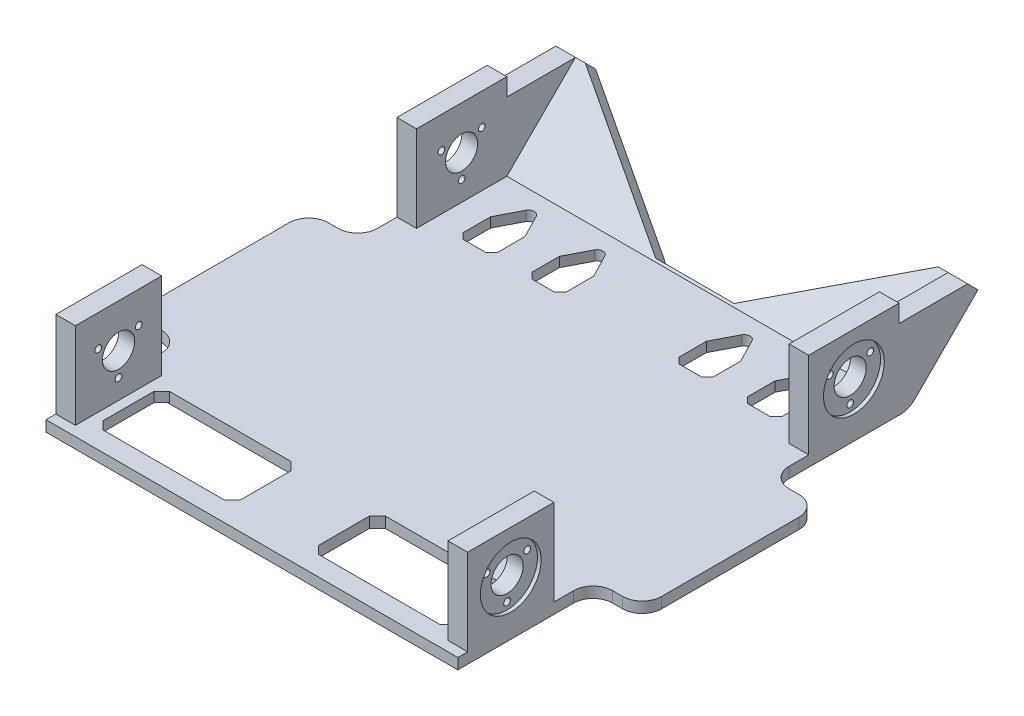
SolidWorks part; units mm, degrees
ref_plane "前视基准面" through (0, 0, 0) normal (0, 0, 1) x (1, 0, 0)
ref_plane "上视基准面" through (0, 0, 0) normal (0, 1, 0) x (1, 0, 0)
ref_plane "右视基准面" through (0, 0, 0) normal (1, 0, 0) x (0, 0, -1)
sketch "草图1" plane through (0, 0, 0) normal (0, 1, 0) x (1, 0, 0)
  line L0 (0, 0) -> (210, 0)
  line L1 (210, 0) -> (210, -230)
  line L2 (210, -230) -> (0, -230)
  line L3 (0, -230) -> (0, 0)
  line L4 (0, 0) -> (3, 0)
  line L5 (0, 0) -> (5, 0)
  line L6 (5, 0) -> (5, -230)
  line L7 (210, 0) -> (205, 0)
  line L8 (205, 0) -> (205, -230)
  line L9 (0, 0) -> (0, -10)
  line L10 (0, -10) -> (210, -10)
  line L11 (210, -230) -> (210, -220)
  line L12 (210, -220) -> (0, -220)
  line L13 (5, -10) -> (85, -10)
  line L14 (85, -10) -> (85, -44)
  line L15 (85, -44) -> (5, -44)
  line L16 (205, -10) -> (125, -10)
  line L17 (125, -10) -> (125, -44)
  line L18 (125, -44) -> (205, -44)
  line L19 (5, -220) -> (5, -186)
  line L20 (5, -186) -> (85, -186)
  line L21 (85, -186) -> (85, -220)
  line L22 (85, -220) -> (5, -220)
  line L23 (205, -220) -> (125, -220)
  line L24 (125, -220) -> (125, -186)
  line L25 (125, -186) -> (205, -186)
  line L26 (205, -186) -> (205, -220)
  line L27 (5, -10) -> (5, -44)
  line L28 (205, -44) -> (205, -10)
extrude "凸台-拉伸1" add sketch "草图1" along normal blind 5.5 contours L24 L25 L8 L18 L17 L10 L14 L15 L6 L20 L21 L12 | L3 L10 L6 L0 | L12 L6 L10 L3 | L6 L10 L8 L0 | L12 L1 L10 L8 | L8 L10 L1 L0 | L8 L12 L6 L2 | L6 L12 L3 L2 | L1 L12 L8 L2 region at (2.5, 0, 5) region at (2.5, 0, 115) region at (105, 0, 5) region at (2.5, 0, 225) region at (207.5, 0, 5) region at (105, 0, 225) region at (105, 0, 115) region at (207.5, 0, 115) region at (207.5, 0, 225)
sketch "草图3" plane through (0, 5.5, 0) normal (0, 1, 0) x (1, 0, 0)
  line L0 (85, -10) -> (85, 0)
  line L1 (0, 0) -> (210, 0) construction
  line L2 (85, 0) -> (85, -5)
  line L3 (85, -5) -> (0, -5)
  line L4 (0, -230) -> (0, 0) construction
  line L5 (0, -5) -> (0, -46.0662)
  line L6 (0, -46.0662) -> (0, -51.0662)
  line L7 (0, -51.0662) -> (5, -51.0662)
  line L8 (5, -51.0662) -> (5, -5)
  line L9 (105, 0) -> (105, -230)
  line L10 (210, -230) -> (0, -230) construction
  line L11 (5, -220) -> (5, -225)
  line L12 (5, -225) -> (0, -225)
  line L13 (0, -225) -> (0, -181)
  line L14 (0, -181) -> (5, -181)
  line L15 (5, -181) -> (5, -220)
  line L16 (210, -181) -> (205, -181)
  line L17 (210, -225) -> (210, -181)
  line L18 (205, -225) -> (210, -225)
  line L19 (205, -220) -> (205, -225)
  line L20 (205, -181) -> (205, -220)
  line L21 (5, -5) -> (5, -51.0662)
  line L22 (0, -51.0662) -> (0, -5)
  line L23 (210, -46.0662) -> (210, -51.0662)
  line L24 (210, -51.0662) -> (205, -51.0662)
  line L25 (205, -51.0662) -> (205, -5)
  line L26 (210, -5) -> (210, -46.0662)
  line L27 (205, -5) -> (210, -5)
extrude "凸台-拉伸2" add sketch "草图3" along normal blind 44 contours L7 L8 L17 L3 L10 | L15 L14 L10 L12 L11 L26 | L16 L20 L6 L19 L18 L2 | L27 L25 L22 L24 L2 region at (2.5, 5.5, 28.0331) region at (2.5, 5.5, 203) region at (207.5, 5.5, 203) region at (207.5, 5.5, 28.0331)
sketch "草图4" plane through (0, 0, 0) normal (-1, 0, 0) x (0, 0, 1)
  line L0 (5, 49.5) -> (51.0662, 5.5)
  line L1 (181, 49.5) -> (225, 5.5)
  circle A1 centre (203, 27.5) radius 17
  circle A2 centre (28.0331, 27.5) radius 15
  circle A3 centre (28.0331, 27.5) radius 8.2
  circle A4 centre (28.0331, 27.5) radius 11.9
  circle A5 centre (28.0331, 15.6) radius 1.7
  circle A6 centre (17.7274, 33.45) radius 1.7
  circle A7 centre (38.3388, 33.45) radius 1.7
  point P24 (28.0331, 27.5)
  dimension "D1" = 3
extrude "切除-拉伸1" cut sketch "草图4" against normal through all both and the other way through all contours A4 A6 | A4 A6 | A4 A7 | A4 A7 | A4 A5 | A4 A5 | L0 A3 | L0 A3 region at (0, 30.0167, 30.4369) region at (0, 24.9833, 25.6293) region at (0, 33.7996, 38.9443) region at (0, 33.0785, 37.6954) region at (0, 33.0785, 18.3708) region at (0, 33.7996, 17.1219) region at (0, 14.9008, 28.0331) region at (0, 16.3429, 28.0331)
sketch "草图5" plane through (0, 0, 0) normal (-1, 0, 0) x (0, 0, 1)
  circle A1 centre (28.0331, 27.5) radius 15.5
extrude "切除-拉伸3" cut sketch "草图5" against normal blind 1.9
sketch "草图6" plane through (210, 0, 0) normal (1, 0, 0) x (0, 0, -1)
  circle A0 centre (-28.0331, 27.5) radius 15.5
extrude "切除-拉伸4" cut sketch "草图6" against normal blind 1.9
sketch "草图7" plane through (0, 0, 0) normal (-1, 0, 0) x (0, 0, 1)
  line L0 (181, 49.5) -> (225, 5.5)
  line L1 (203, 27.5) -> (203, 15.6)
  circle A0 centre (203, 27.5) radius 11.9
  circle A1 centre (203, 27.5) radius 8.2
  circle A2 centre (203, 15.6) radius 1.7
  circle A3 centre (192.6943, 33.45) radius 1.7
  circle A4 centre (213.3057, 33.45) radius 1.7
  point P15 (203, 27.5)
  dimension "D1" = 3
extrude "切除-拉伸5" cut sketch "草图7" against normal through all both and the other way through all contours A0 A3 | A0 A3 | A0 A4 | A0 A4 | A0 A2 L1 | L1 A2 A0 | A0 A2 | L0 A1 | L0 A1 L1 | L1 A1 L0 region at (0, 29.9609, 205.4609) region at (0, 25.8594, 199.0393) region at (0, 33.7996, 213.9112) region at (0, 33.0785, 212.6623) region at (0, 33.0785, 193.3377) region at (0, 33.7996, 192.0888) region at (0, 22.5783, 205.0386) region at (0, 16.3429, 203.7042) region at (0, 16.3429, 202.2958) region at (0, 14.9008, 203)
sketch "草图8" plane through (0, 0, 0) normal (-1, 0, 0) x (0, 0, 1)
  circle A0 centre (203, 27.5) radius 15.5
extrude "切除-拉伸6" cut sketch "草图8" against normal blind 1.9
sketch "草图9" plane through (210, 0, 0) normal (1, 0, 0) x (0, 0, -1)
  circle A0 centre (-203, 27.5) radius 15.5
extrude "切除-拉伸7" cut sketch "草图9" against normal blind 1.9
sketch "草图10" plane through (0, 5.5, 0) normal (0, 1, 0) x (1, 0, 0)
  line L0 (5, -10) -> (15, -10)
  line L1 (5, -10) -> (85, -10) construction
  line L2 (15, -10) -> (15, -220)
  line L3 (85, -220) -> (5, -220) construction
  line L4 (15, -220) -> (5, -220)
  line L5 (5, -220) -> (5, -186)
  line L6 (5, -181) -> (5, -225) construction
  line L7 (5, -181) -> (5, -186) construction
  line L8 (5, -186) -> (15, -186)
  line L9 (5, -186) -> (85, -186) construction
  line L10 (5, -10) -> (5, -44)
  line L11 (5, -44) -> (15, -44)
  line L12 (85, -44) -> (5, -44) construction
  line L13 (205, -10) -> (195, -10)
  line L14 (125, -10) -> (205, -10) construction
  line L15 (195, -10) -> (195, -220)
  line L16 (205, -220) -> (125, -220) construction
  line L17 (195, -220) -> (205, -220)
  line L18 (205, -220) -> (205, -186)
  line L19 (205, -186) -> (195, -186)
  line L20 (125, -186) -> (205, -186) construction
  line L21 (205, -10) -> (205, -44)
  line L22 (205, -44) -> (195, -44)
  line L23 (125, -44) -> (205, -44) construction
  line M7 (5, -10) -> (85, -10)
  line M9 (85, -44) -> (5, -44)
  line M15 (5, -186) -> (85, -186)
  line M17 (85, -220) -> (5, -220)
  line M25 (205, -220) -> (125, -220)
  line M27 (125, -186) -> (205, -186)
  line M33 (205, -44) -> (125, -44)
  line M35 (125, -10) -> (205, -10)
extrude "凸台-拉伸3" add sketch "草图10" against normal blind 5 contours L21 L15 M35 M33 | L10 L2 M7 M9 | L5 L2 M17 M15 | L18 L15 M25 M27 region at (10, 5.5, 203) region at (10, 5.5, 27) region at (200, 5.5, 27) region at (200, 5.5, 203)
sketch "草图11" plane through (0, 5.5, 0) normal (0, 1, 0) x (1, 0, 0)
  line L0 (15, -10) -> (5, -10)
  line L1 (5, -51.0662) -> (5, -5) construction
  line L2 (10, -10) -> (10, -51.0662)
  line L3 (10, -51.0662) -> (5, -51.0662)
  line L4 (5, -51.0662) -> (5, -5)
  line L5 (5, -5) -> (10, -5)
  line L6 (10, -5) -> (10, -10)
  line L7 (10, -51.0662) -> (10, -230)
  line L8 (210, -230) -> (0, -230) construction
  line L9 (5, -225) -> (10, -225)
  line L10 (5, -181) -> (10, -181)
  line L11 (10, -181) -> (10, -225)
  line L12 (5, -181) -> (5, -225)
  line L13 (195, -10) -> (205, -10)
  line L14 (205, -51.0662) -> (205, -5) construction
  line L15 (200, -10) -> (200, -51.0662)
  line L16 (200, -51.0662) -> (205, -51.0662)
  line L17 (205, -51.0662) -> (205, -5)
  line L18 (205, -5) -> (200, -5)
  line L19 (200, -5) -> (200, -10)
  line L20 (200, -225) -> (205, -225)
  line L21 (205, -225) -> (205, -181)
  line L22 (205, -181) -> (200, -181)
  line L23 (200, -181) -> (200, -225)
  line M6 (5, -181) -> (5, -225)
  line M12 (205, -225) -> (205, -181)
  line M16 (205, -51.0662) -> (205, -5)
  line M22 (5, -5) -> (5, -51.0662)
extrude "凸台-拉伸4" add sketch "草图11" along normal blind 44 contours L3 L2 L0 M22 | L6 L5 L0 M22 | L18 L19 L13 M16 | L15 L16 L13 M16 | L10 L9 L7 M6 | L22 L23 L20 M12 region at (7.5, 5.5, 30.5331) region at (7.5, 5.5, 203) region at (7.5, 5.5, 7.5) region at (202.5, 5.5, 7.5) region at (202.5, 5.5, 30.5331) region at (202.5, 5.5, 203)
sketch "草图12" plane through (1.9, 0, 0) normal (-1, 0, 0) x (0, 0, 1)
  circle A0 centre (17.7274, 33.45) radius 1.7
  circle A1 centre (38.3388, 33.45) radius 1.7
  circle A2 centre (28.0331, 15.6) radius 1.7
  circle A3 centre (28.0331, 27.5) radius 8.2
  circle A4 centre (192.6943, 33.45) radius 1.7
  circle A5 centre (213.3057, 33.45) radius 1.7
  circle A6 centre (203, 15.6) radius 1.7
  circle A7 centre (203, 27.5) radius 8.2
extrude "切除-拉伸8" cut sketch "草图12" against normal through all both and the other way through all
sketch "草图13" plane through (210, 0, 0) normal (1, 0, 0) x (0, 0, -1)
  line L0 (-5, 5.5) -> (14.6466, 25.1466)
sketch "草图15" plane through (210, 0, 0) normal (1, 0, 0) x (0, 0, -1)
  line L0 (-5, 5.5) -> (-5, 40.5)
  line L1 (-5, 49.5) -> (-5, 5.5) construction
  line L2 (-5, 40.5) -> (31.0178, 40.5)
ref_plane "基准面5" through (0, 5.25, 5.25) normal (0, 0.7071, 0.7071) x (1, 0, 0)
sketch "草图17" plane through (0, 5.25, 5.25) normal (0, 0.7071, 0.7071) x (1, 0, 0)
  line L0 (210, 0.3536) -> (210, 49.8474)
  line L1 (210, 49.8474) -> (0, 49.8474)
  line L2 (0, 49.8474) -> (0, 0.3536)
  line L3 (0, 0.3536) -> (210, 0.3536)
extrude "凸台-拉伸5" add sketch "草图17" against normal through all
sketch "草图18" plane through (0, 0, 0) normal (-1, 0, 0) x (0, 0, 1)
  line L0 (-29.9975, 40.4975) -> (5, 40.5)
  line L1 (5, 40.5) -> (5, 5.5)
  line L2 (5, 5.5) -> (-29.9975, 40.4975)
extrude "凸台-拉伸6" add sketch "草图18" against normal blind 10
sketch "草图19" plane through (210, 0, 0) normal (1, 0, 0) x (0, 0, -1)
  line L0 (30, 40.5) -> (-5, 40.5)
  line L1 (-5, 40.5) -> (31.0178, 40.5) construction
  line L2 (40.3406, 50.8406) -> (-50.8406, -40.3406) construction
  line L3 (-5, 40.5) -> (-5, 5.5)
  line L4 (-5, 5.5) -> (30, 40.5)
extrude "凸台-拉伸8" add sketch "草图19" against normal blind 10
sketch "草图20" plane through (0, 5.25, 5.25) normal (0, 0.7071, 0.7071) x (1, 0, 0)
  line L0 (15, -3.182) -> (15, 49.8474)
  line L1 (200, 49.8474) -> (10, 49.8474) construction
  line L4 (125, 49.8474) -> (85, 49.8474)
  line L5 (85, 1.6082) -> (125, 1.6082)
  line L6 (125, 1.6082) -> (125, 49.8474)
  line L7 (85, 49.8474) -> (125, 49.8474)
  line L8 (85, 1.6082) -> (85, 49.8474)
  line L9 (15, 49.8474) -> (85, 1.6082)
  line L10 (195, -3.182) -> (195, 49.8474)
  line L11 (195, 49.8474) -> (125, 1.6082)
  line L12 (15, 1.6082) -> (85, 1.6082)
  line L13 (125, 1.6082) -> (195, 1.6082)
  line L14 (195, 1.6082) -> (195, 49.8474)
  line M4 (200, 49.8474) -> (10, 49.8474)
extrude "切除-拉伸9" cut sketch "草图20" against normal blind 10 contours L9 L8 M4 | L8 L5 L6 M4 | L11 L6 M4 region at (61.6667, 29.1274, -18.6274) region at (105, 23.4423, -12.9423) region at (148.3333, 29.1274, -18.6274)
sketch "草图21" plane through (0, 5.5, 0) normal (0, 1, 0) x (1, 0, 0)
  line L1 (15, -10) -> (85, -10) construction
  line L4 (125, -10) -> (195, -10) construction
  line L6 (32.5, -10) -> (15, -44)
  line L7 (32.5, -10) -> (50, -44)
  line L8 (85, -44) -> (15, -44) construction
  line L9 (50, -44) -> (67.5, -10)
  line L10 (67.5, -10) -> (85, -44)
  line L11 (125, -44) -> (142.5, -10)
  line L12 (142.5, -10) -> (160, -44)
  line L14 (160, -44) -> (177.5, -10)
  line L15 (177.5, -10) -> (195, -44)
  line L16 (15, -44) -> (15, -10)
  line L17 (15, -10) -> (32.5, -10)
  line L18 (32.5, -10) -> (67.5, -10)
  line L19 (67.5, -10) -> (85, -10)
  line L20 (85, -10) -> (85, -44)
  line L21 (125, -44) -> (125, -10)
  line L22 (125, -10) -> (142.5, -10)
  line L23 (142.5, -10) -> (177.5, -10)
  line L24 (177.5, -10) -> (195, -10)
  line L25 (195, -10) -> (195, -44)
  line L26 (41.25, -27) -> (41.25, -44)
  line L27 (58.75, -27) -> (58.75, -44)
  line L28 (151.25, -27) -> (151.25, -44)
  line L29 (125, -44) -> (195, -44) construction
  line L30 (168.75, -27) -> (168.75, -44)
  line L31 (41.25, -44) -> (58.75, -44)
  line L32 (151.25, -44) -> (168.75, -44)
  line M21 (15, -44) -> (15, -10)
  line M22 (15, -10) -> (85, -10)
  line M23 (85, -10) -> (85, -44)
  line M24 (85, -44) -> (15, -44)
  line M29 (125, -10) -> (195, -10)
  line M30 (195, -10) -> (195, -44)
  line M31 (195, -44) -> (125, -44)
  line M32 (125, -44) -> (125, -10)
extrude "凸台-拉伸11" add sketch "草图21" against normal blind 5 contours L6 M22 M21 | L7 L9 M22 | L7 L26 M24 | L27 L9 M24 | L10 M22 M23 | L11 M32 M29 | L12 L14 M29 | L15 M29 M30 | L30 L14 M31 | L12 L28 M31 region at (50, 5.5, 21.3333) region at (20.8333, 5.5, 21.3333) region at (44.1667, 5.5, 38.3333) region at (79.1667, 5.5, 21.3333) region at (55.8333, 5.5, 38.3333) region at (130.8333, 5.5, 21.3333) region at (160, 5.5, 21.3333) region at (154.1667, 5.5, 38.3333) region at (189.1667, 5.5, 21.3333) region at (165.8333, 5.5, 38.3333)
sketch "草图22" plane through (0, 0, 0) normal (-1, 0, 0) x (0, 0, 1)
  line L0 (0, 0.5) -> (0, 0)
  line L1 (0, 0) -> (-0.25, 0.25)
  line L2 (-0.25, 0.25) -> (0, 0.5)
extrude "凸台-拉伸13" add sketch "草图22" against normal blind 210
fillet "圆角1" radius 10 1 edges at (105, 0, 0)
sketch "草图23" plane through (0, 5.5, 0) normal (0, 1, 0) x (1, 0, 0)
  line L0 (23.75, -27) -> (23.75, -44)
  line L1 (32.5, -10) -> (15, -44) construction
  line L2 (41.25, -44) -> (15, -44) construction
  line L3 (23.75, -44) -> (15, -44)
  line L4 (15, -44) -> (23.75, -27)
  line L5 (76.25, -27) -> (76.25, -44)
  line L6 (67.5, -10) -> (85, -44) construction
  line L7 (85, -44) -> (58.75, -44) construction
  line L8 (76.25, -44) -> (85, -44)
  line L9 (85, -44) -> (76.25, -27)
  line L10 (133.75, -27) -> (133.75, -44)
  line L11 (125, -44) -> (142.5, -10) construction
  line L12 (125, -44) -> (151.25, -44) construction
  line L13 (133.75, -44) -> (125, -44)
  line L14 (125, -44) -> (133.75, -27)
  line L15 (186.25, -27) -> (186.25, -44)
  line L16 (177.5, -10) -> (195, -44) construction
  line L17 (168.75, -44) -> (195, -44) construction
  line L18 (186.25, -44) -> (195, -44)
  line L19 (195, -44) -> (186.25, -27)
extrude "凸台-拉伸14" add sketch "草图23" against normal blind 5 contours L4 L0 L3 | L9 L5 L8 | L14 L10 L13 | L19 L15 L18
sketch "草图25" plane through (0, 5.5, 0) normal (0, 1, 0) x (1, 0, 0)
  line L0 (105, 21.1547) -> (105, -242.7807) construction
  line L1 (-56.829, -116.0331) -> (264.4539, -116.0331) construction
  line L2 (0, -181) -> (0, -51.0662) construction
  point P8 (0, -116.0331)
sketch "草图26" plane through (0, 5.5, 0) normal (0, 1, 0) x (1, 0, 0)
  line L0 (210, -51.0662) -> (210, -181) construction
  line L1 (210, -161.0331) -> (235, -161.0331)
  line L2 (210, -161.0331) -> (210, -71.0331)
  line L3 (210, -71.0331) -> (235, -71.0331)
  line L4 (235, -161.0331) -> (235, -71.0331)
  line L7 (105, 21.1547) -> (105, -242.7807)
  line L8 (-25, -161.0331) -> (-25, -71.0331)
  line L9 (0, -71.0331) -> (-25, -71.0331)
  line L10 (0, -161.0331) -> (0, -71.0331)
  line L11 (0, -161.0331) -> (-25, -161.0331)
  line L12 (-56.829, -116.0331) -> (264.4539, -116.0331) construction
  dimension "D1" = 25
  dimension "D2" = 90
  dimension "D3" = 45
extrude "凸台-拉伸15" add sketch "草图26" against normal blind 5.5 contours L11 L10 L9 L8 | L1 L4 L3 L2 region at (222.5, 5.5, 116.0331) region at (-12.5, 5.5, 116.0331)
fillet "圆角2" radius 10 8 edges at (210, 2.75, 161.0331) (235, 2.75, 161.0331) (235, 2.75, 71.0331) (210, 2.75, 71.0331) (0, 2.75, 71.0331) (-25, 2.75, 71.0331) (-25, 2.75, 161.0331) (0, 2.75, 161.0331)
chamfer "倒角1" distance 4 angle 45 8 edges at (15, 3, 220) (85, 2.75, 220) (85, 2.75, 186) (15, 3, 186) (125, 2.75, 186) (125, 2.75, 220) (195, 3, 220) (195, 3, 186)
chamfer "倒角2" distance 3 angle 45 8 edges at (41.25, 3, 44) (76.25, 3, 44) (151.25, 3, 44) (168.75, 3, 44) (23.75, 3, 44) (58.75, 3, 44) (133.75, 3, 44) (186.25, 3, 44)
fillet "圆角3" radius 3 4 edges at (177.5, 3, 10) (142.5, 3, 10) (67.5, 3, 10) (32.5, 3, 10)
